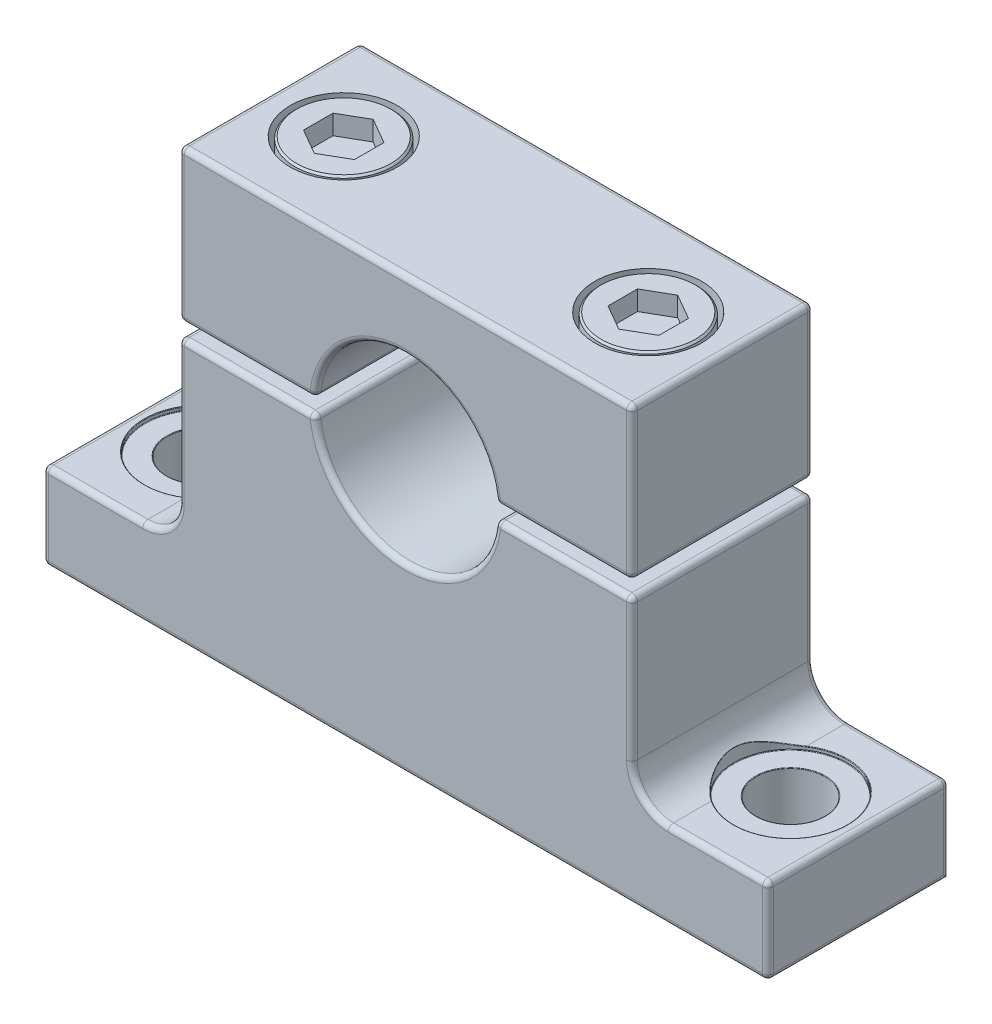
SolidWorks part; units mm, degrees
material "6061-T6 (SS)"
ref_plane "Front" through (0, 0, 0) normal (0, 0, 1) x (1, 0, 0)
ref_plane "Top" through (0, 0, 0) normal (0, 1, 0) x (1, 0, 0)
ref_plane "Right" through (0, 0, 0) normal (1, 0, 0) x (0, 0, -1)
sketch "Sketch1" plane through (0, 0, 0) normal (0, 0, 1) x (1, 0, 0)
  line L0 (0, 30.1625) -> (0, 0) construction
  line L1 (-25.4, 0) -> (25.4, 0) construction
  line L2 (0, 0) -> (0, 19.05) construction
  line L3 (-20.6375, 0) -> (20.6375, 0) construction
  line L4 (18.2245, 0) -> (23.0505, 0) construction
  line L5 (23.0505, 0) -> (23.0505, 1.27) construction
  line L6 (18.2245, 0) -> (18.2245, 1.27) construction
  line L7 (-18.2245, 0) -> (-18.2245, 1.27) construction
  line L8 (-23.0505, 0) -> (-23.0505, 1.27) construction
  line L9 (-18.2245, 0) -> (-23.0505, 0) construction
  line L10 (-15.875, 19.05) -> (15.875, 19.05) construction
  line L11 (-15.875, 18.542) -> (15.875, 18.542) construction
  line L12 (-15.875, 19.558) -> (15.875, 19.558) construction
  line L13 (17.8435, 0) -> (17.8435, 1.27) construction
  line L14 (23.4315, 0) -> (23.4315, 1.27) construction
  line L15 (-17.8435, 0) -> (-17.8435, 1.27) construction
  line L16 (-23.4315, 0) -> (-23.4315, 1.27) construction
  line L17 (-11.0713, 18.542) -> (11.0713, 18.542) construction
  line L18 (-11.0713, 19.558) -> (11.0713, 19.558) construction
  line L19 (-11.0713, 19.05) -> (11.0713, 19.05) construction
  line L20 (-25.4, 0) -> (-25.4, 6.0325) construction
  line L21 (-25.4, 6.0325) -> (-15.875, 6.0325) construction
  line L22 (-15.875, 18.542) -> (-15.875, 6.0325) construction
  line L23 (-15.875, 19.558) -> (-15.875, 30.1625) construction
  line L24 (-15.875, 30.1625) -> (15.875, 30.1625) construction
  line L25 (25.4, 0) -> (25.4, 6.0325) construction
  line L26 (25.4, 6.0325) -> (15.875, 6.0325) construction
  line L27 (15.875, 18.542) -> (15.875, 6.0325) construction
  line L28 (15.875, 19.558) -> (15.875, 30.1625) construction
  line L29 (0, 30.1625) -> (0, 25.9969) construction
  line L30 (0.3175, 25.9969) -> (-0.3175, 25.9969) construction
  line L31 (15.875, 6.0325) -> (15.875, 0) construction
  line L32 (-20.6375, 0) -> (-20.6375, 6.0325) construction
  line L33 (0, 25.4) -> (15.875, 25.4) construction
  line L34 (0, 12.7) -> (15.875, 12.7) construction
  circle A0 centre (0, 19.05) radius 6.35 construction
  arc A1 (-18.415, 6.0325) -> (-15.875, 8.5725) centre (-18.415, 8.5725) ccw construction
  arc A2 (18.415, 6.0325) -> (15.875, 8.5725) centre (18.415, 8.5725) cw construction
  point P5 (0, 0)
  point P9 (0, 19.05)
  point P11 (0, 0)
  point P12 (20.6375, 0)
  point P13 (-20.6375, 0)
  point P16 (20.6375, 0)
  point P37 (0, 18.542)
  point P40 (0, 19.558)
  point P60 (0, 25.9969)
  point P64 (20.6375, 6.0325)
  dimension "D1" = 1.27
  dimension "D8" = 6.0325
  dimension "D12" = 0.635
  dimension "Radius" = 2.54
  dimension "D9" = 4.7625
  dimension "D3" = 0.508
  dimension "D4" = 0.381
  dimension "D5" = 0.381
  dimension "D6" = 0.381
  dimension "D7" = 0.381
sketch "Sketch3" plane through (0, 0, 0) normal (0, 0, 1) x (1, 0, 0)
  line L0 (-15.875, 30.1625) -> (15.875, 30.1625) construction
  line L1 (15.875, 19.558) -> (15.875, 30.1625) construction
  line L2 (-15.875, 19.558) -> (15.875, 19.558) construction
  line L3 (-15.875, 19.558) -> (-15.875, 30.1625) construction
  line L4 (-15.875, 18.542) -> (-15.875, 6.0325) construction
  line L5 (-25.4, 6.0325) -> (-15.875, 6.0325) construction
  line L6 (-25.4, 0) -> (-25.4, 6.0325) construction
  line L7 (-25.4, 0) -> (25.4, 0) construction
  line L8 (25.4, 0) -> (25.4, 6.0325) construction
  line L9 (25.4, 6.0325) -> (15.875, 6.0325) construction
  line L10 (15.875, 18.542) -> (15.875, 6.0325) construction
  line L11 (-15.875, 18.542) -> (15.875, 18.542) construction
  line L12 (-15.875, 30.1625) -> (15.875, 30.1625)
  line L13 (15.875, 19.558) -> (15.875, 30.1625)
  line L14 (-15.875, 19.558) -> (-6.3296, 19.558)
  line L15 (-15.875, 19.558) -> (-15.875, 30.1625)
  line L16 (-15.875, 18.542) -> (-15.875, 8.5725)
  line L17 (-25.4, 6.0325) -> (-18.415, 6.0325)
  line L18 (-25.4, 0) -> (-25.4, 6.0325)
  line L19 (-25.4, 0) -> (25.4, 0)
  line L20 (25.4, 0) -> (25.4, 6.0325)
  line L21 (25.4, 6.0325) -> (18.415, 6.0325)
  line L22 (15.875, 18.542) -> (15.875, 8.5725)
  line L23 (-15.875, 18.542) -> (-6.3296, 18.542)
  line L24 (6.3296, 19.558) -> (15.875, 19.558)
  line L25 (6.3296, 18.542) -> (15.875, 18.542)
  arc A0 (-18.415, 6.0325) -> (-15.875, 8.5725) centre (-18.415, 8.5725) ccw construction
  arc A1 (15.875, 8.5725) -> (18.415, 6.0325) centre (18.415, 8.5725) ccw construction
  circle A2 centre (0, 19.05) radius 6.35 construction
  arc A3 (-18.415, 6.0325) -> (-15.875, 8.5725) centre (-18.415, 8.5725) ccw
  arc A4 (15.875, 8.5725) -> (18.415, 6.0325) centre (18.415, 8.5725) ccw
  arc A5 (6.3296, 19.558) -> (-6.3296, 19.558) centre (0, 19.05) ccw
  arc A6 (-6.3296, 18.542) -> (6.3296, 18.542) centre (0, 19.05) ccw
extrude "Boss-Extrude1" add sketch "Sketch3" against normal blind 12.7
sketch "Sketch4" plane through (0, 0, 0) normal (0, -1, 0) x (1, 0, 0)
  line L0 (-25.4, 0) -> (-25.4, -12.7) construction
  line L1 (-25.4, 0) -> (-15.875, 0) construction
  line L2 (-25.4, -6.35) -> (25.4, -6.35) construction
  line L3 (25.4, -12.7) -> (25.4, 0) construction
  line L4 (-20.6375, 0) -> (-20.6375, -12.7) construction
  line L5 (20.6375, 0) -> (20.6375, -12.7) construction
  line L6 (-25.4, -12.7) -> (25.4, -12.7) construction
  line L7 (0, 0) -> (0, -12.7) construction
  circle A0 centre (-20.6375, -6.35) radius 2.413
  circle A1 centre (20.6375, -6.35) radius 2.413
  point P7 (-25.4, -6.35)
  dimension "D1" = 4.826
extrude "Cut-Extrude1" cut sketch "Sketch4" against normal through all
sketch "Sketch6" plane through (0, 6.0325, 0) normal (0, 1, 0) x (1, 0, 0)
  line L0 (0, 0) -> (0, 12.7) construction
  line L1 (-25.4, 0) -> (25.4, 0) construction
  line L2 (15.875, 12.7) -> (-15.875, 12.7) construction
  circle A1 centre (-20.6375, 6.35) radius 2.413 construction
  circle A2 centre (-20.6375, 6.35) radius 2.413
  circle A4 centre (-20.6375, 6.35) radius 2.794
  circle A5 centre (20.6375, 6.35) radius 2.794
  dimension "D1" = 0.381
sketch "Sketch7" plane through (0, 0, 0) normal (0, 0, 1) x (1, 0, 0)
  line L0 (-25.4, 5.7785) -> (25.4, 5.7785) construction
  line L1 (-15.875, 18.542) -> (-15.875, 0) construction
  line L2 (-25.4, 0) -> (25.4, 0) construction
  line L3 (15.875, 18.542) -> (15.875, 0) construction
  line L5 (-25.4, 0) -> (-25.4, 6.0325) construction
  line L6 (-25.4, 6.0325) -> (-15.875, 6.0325) construction
  line L7 (25.4, 0) -> (25.4, 6.0325) construction
  line L8 (-20.6375, 6.0325) -> (-20.6375, 5.7785) construction
  line L9 (20.6375, 6.0325) -> (20.6375, 5.7785) construction
  line L10 (25.4, 6.0325) -> (15.875, 6.0325) construction
  dimension "D1" = 0.254
sketch "Sketch8" plane through (0, 18.542, 0) normal (0, 1, 0) x (1, 0, 0)
  line L0 (0, 0) -> (0, 12.7) construction
  line L1 (15.875, 12.7) -> (-15.875, 12.7) construction
  circle A0 centre (-20.6375, 6.35) radius 2.794 construction
  circle A1 centre (20.6375, 6.35) radius 2.794 construction
  circle A2 centre (-20.6375, 6.35) radius 2.794 construction
  circle A3 centre (20.6375, 6.35) radius 2.794 construction
  circle A4 centre (-20.6375, 6.35) radius 3.9751
  circle A5 centre (20.6375, 6.35) radius 3.9751
  dimension "CounterBoreID" = 7.9502
extrude "Cut-Extrude3" cut sketch "Sketch8" against normal up to vertex (12.7635 mm away) up to point (-20.6375, 5.7785, 0)
sketch "Sketch10" plane through (0, 30.1625, 0) normal (0, 1, 0) x (1, 0, 0)
  line L0 (-15.875, 12.7) -> (-15.875, 0) construction
  line L1 (15.875, 12.7) -> (15.875, 0) construction
  line L2 (-15.875, 12.7) -> (-15.875, 0) construction
  line L3 (15.875, 12.7) -> (15.875, 0) construction
  line L4 (-14.097, 12.7) -> (-14.097, 0) construction
  line L5 (0, 0) -> (0, 12.7) construction
  line L6 (14.097, 12.7) -> (14.097, 0) construction
  circle A0 centre (-10.668, 6.35) radius 2.0828 construction
  circle A1 centre (10.668, 6.35) radius 2.3368
  circle A2 centre (-10.668, 6.35) radius 2.3368
  circle A3 centre (10.668, 6.35) radius 2.0828 construction
  circle A4 centre (-10.668, 6.35) radius 3.429 construction
  circle A5 centre (10.668, 6.35) radius 3.429 construction
extrude "Cut-Extrude4" cut sketch "Sketch10" against normal through all
ref_plane "Plane1" through (0, 0, -6.35) normal (0, 0, 1) x (1, 0, 0)
sketch "Sketch12" plane through (0, 30.1625, 0) normal (0, 1, 0) x (1, 0, 0)
  line L0 (0, 12.7) -> (0, 0) construction
  circle A0 centre (-10.668, 6.35) radius 3.6195 construction
  circle A1 centre (10.668, 6.35) radius 3.7465
  circle A2 centre (-10.668, 6.35) radius 3.7465
  circle A3 centre (10.668, 6.35) radius 3.6195 construction
  dimension "D2" = 7.493
extrude "Cut-Extrude5" cut sketch "Sketch12" against normal blind 4.5466
sketch "Sketch13" plane through (0, 0, 0) normal (0, 1, 0) x (1, 0, 0)
  line L0 (-10.668, 12.7) -> (-10.668, 0) construction
  line L1 (15.875, 12.7) -> (-15.875, 12.7) construction
  line L2 (0, 12.7) -> (0, 0) construction
  line L3 (10.668, 12.7) -> (10.668, 0) construction
  circle A0 centre (-10.668, 6.35) radius 2.0066 construction
  point P2 (-10.668, 6.35)
  point P9 (-10.668, 12.7)
  point P10 (-10.668, 0)
  point P17 (10.668, 12.7)
  point P18 (10.668, 0)
  dimension "D1" = 4.0132
sketch "Sketch15" plane through (0, 0, -6.35) normal (0, 0, 1) x (1, 0, 0)
  line L0 (-10.668, 12.065) -> (-10.668, 30.1625) construction
  line L1 (-10.668, 30.1625) -> (-14.097, 30.1625) construction
  line L2 (-14.097, 30.1625) -> (-14.097, 25.9969) construction
  line L3 (-14.097, 25.9969) -> (-12.7508, 25.9969) construction
  line L4 (-12.7508, 25.9969) -> (-12.7508, 12.065) construction
  line L5 (-12.7508, 12.065) -> (-10.668, 12.065) construction
  line L8 (-15.875, 30.1625) -> (15.875, 30.1625) construction
  line L9 (-10.668, 12.065) -> (-10.668, 30.1625)
  line L10 (-10.668, 30.1625) -> (-14.097, 30.1625)
  line L11 (-14.097, 30.1625) -> (-14.097, 25.9969)
  line L12 (-14.097, 25.9969) -> (-12.7508, 25.9969)
  line L13 (-12.7508, 25.9969) -> (-12.7508, 12.065)
  line L14 (-12.7508, 12.065) -> (-10.668, 12.065)
  dimension "D2" = 3.429
  dimension "D1" = 4.1656
  dimension "D3" = 2.0828
  dimension "Screw Length" = 18.0975
revolve "Revolve1" add sketch "Sketch15" angle 360 about L9
chamfer "Chamfer1" distance 0.127 angle 45 1 edges at (-10.668, 30.1625, -9.779)
sketch "Sketch16" plane through (0, 30.1625, 0) normal (0, 1, 0) x (1, 0, 0)
  line L0 (-10.668, 12.7) -> (-10.668, 0) construction
  line L1 (-10.668, 8.4122) -> (-12.4539, 7.3811)
  line L2 (-12.4539, 7.3811) -> (-12.4539, 5.3189)
  line L3 (-12.4539, 5.3189) -> (-10.668, 4.2878)
  line L4 (-10.668, 4.2878) -> (-8.8821, 5.3189)
  line L5 (-8.8821, 5.3189) -> (-8.8821, 7.3811)
  line L6 (-8.8821, 7.3811) -> (-10.668, 8.4122)
  circle A0 centre (-10.668, 6.35) radius 1.7859 construction
  dimension "Hex Size" = 3.5719
extrude "Cut-Extrude6" cut sketch "Sketch16" against normal blind 1.3746
mirror "Mirror1" about plane through (0, 0, 0) normal (1, 0, 0) of bodies 121 119
fillet "Fillet1" radius 0.381 18 edges at (0, 30.1625, -12.7) (-15.875, 30.1625, -6.35) (-15.875, 24.8603, -12.7) (-15.875, 24.8603, 0) (15.875, 24.8603, -12.7) (15.875, 30.1625, -6.35) (15.875, 24.8603, 0) (0, 30.1625, 0) (15.875, 19.558, -6.35) (11.1023, 19.558, -12.7) (-11.1023, 19.558, -12.7) (-15.875, 19.558, -6.35) (-11.1023, 19.558, 0) (11.1023, 19.558, 0) (0, 25.4, -12.7) (0, 25.4, 0) (6.3296, 19.558, -6.35) (-6.3296, 19.558, -6.35)
fillet "Fillet2" radius 0.381 31 edges at (21.9075, 6.0325, -12.7) (16.6189, 6.7764, -12.7) (15.875, 13.5573, 0) (16.6189, 6.7764, 0) (-21.9075, 6.0325, 0) (-16.6189, 6.7764, 0) (-21.9075, 6.0325, -12.7) (-16.6189, 6.7764, -12.7) (15.875, 13.5573, -12.7) (25.4, 0, -6.35) (25.4, 3.0162, -12.7) (25.4, 6.0325, -6.35) (21.9075, 6.0325, 0) (25.4, 3.0162, 0) (0, 0, 0) (-25.4, 3.0162, -12.7) (-25.4, 0, -6.35) (-25.4, 6.0325, -6.35) (-25.4, 3.0162, 0) (-15.875, 13.5573, 0) (-15.875, 13.5573, -12.7) (15.875, 18.542, -6.35) (-15.875, 18.542, -6.35) (-11.1023, 18.542, 0) (11.1023, 18.542, 0) (11.1023, 18.542, -12.7) (-11.1023, 18.542, -12.7) (0, 12.7, -12.7) (0, 12.7, 0) (6.3296, 18.542, -6.35) (-6.3296, 18.542, -6.35)
fillet "Fillet3" radius 0.0381 8 edges at (-24.6126, 5.7785, -6.35) (24.6126, 5.7785, -6.35) (24.6126, 6.0325, -6.35) (16.6835, 6.7142, -6.7586) (23.0505, 5.7785, -6.35) (-16.6705, 6.7264, -6.0967) (-24.6126, 6.0325, -6.35) (-23.0505, 5.7785, -6.35)
ref_plane "Contact Plane 1" through (0, 0, -6.35) normal (0, 0, -1) x (-1, 0, 0)
ref_plane "Contact Plane 2" through (0, 0, 0) normal (-1, 0, 0) x (0, 0, 1)
ref_plane "Contact Plane 3" through (0, 15.0812, 0) normal (0, 1, 0) x (1, 0, 0)
ref_plane "Contact Plane 4" through (0, 30.1625, 0) normal (0, 1, 0) x (1, 0, 0)
ref_plane "Contact Plane 5" through (0, 0, 0) normal (0, -1, 0) x (-1, 0, 0)
ref_plane "Contact Plane 6" through (25.4, 0, 0) normal (1, 0, 0) x (0, 0, -1)
ref_plane "Contact Plane 7" through (-25.4, 0, 0) normal (-1, 0, 0) x (0, 0, 1)
ref_axis "Center Axis 1" through (0, 54.8037, -6.35) along (0, -1, 0)
ref_axis "Center Axis 2" through (0, 15.0812, -33.3184) along (0, 0, 1)
ref_axis "Center Axis 3" through (69.4309, 15.0813, -6.35) along (-1, 0, 0)
equation "\"D8@Sketch1\"=\"Oall Ht@Sketch1\"*.20"
equation "\"D1@Sketch4\"= \"HoldDia@Sketch1\""
equation "\"D1@Cut-Extrude5\"=\"HeadDp@Sketch1\"+.015"
equation "\"D1@Sketch15\"=\"HeadDp@Sketch1\""
equation "\"D3@Sketch15\"=\"ThrdDia@Sketch10\"*.5"
equation "\"D1@Cut-Extrude6\"= \"HeadDp@Sketch1\"*.33"
equation "\"D2@Sketch12\"=\"Head Dia@Sketch10\"+.025"
equation "\"D2@Sketch15\"=\"Head Dia@Sketch10\"*.50"
